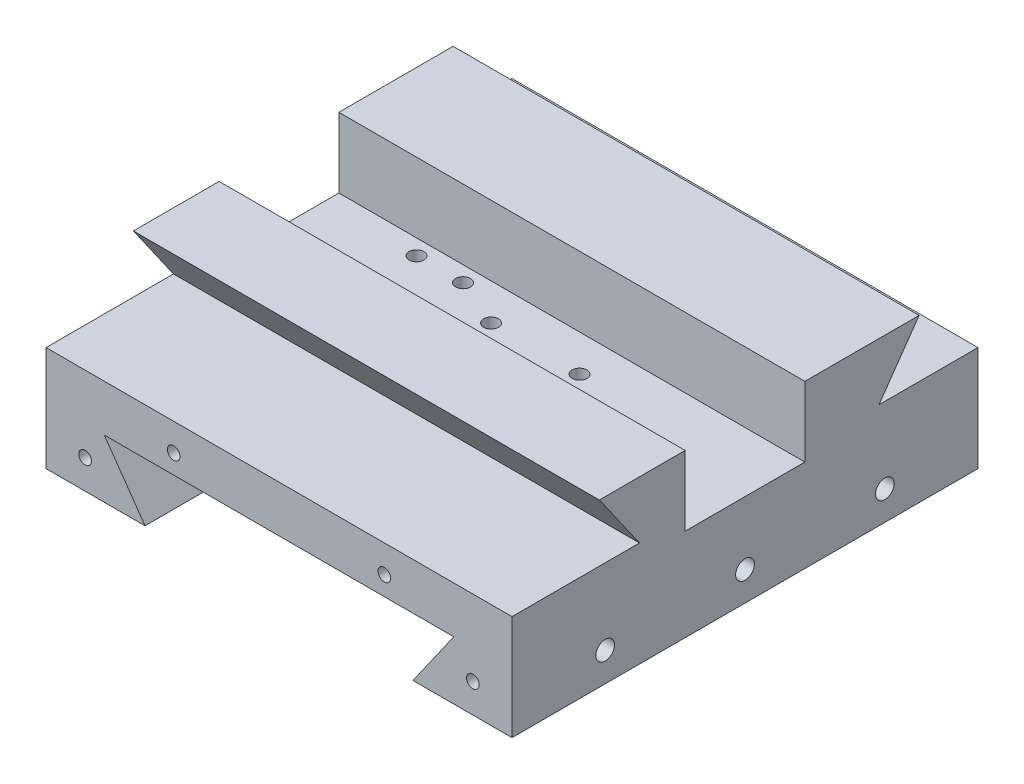
SolidWorks part; units mm, degrees
material "Ductile Iron"
ref_plane "Front Plane" through (0, 0, 0) normal (0, 0, 1) x (1, 0, 0)
ref_plane "Top Plane" through (0, 0, 0) normal (0, 1, 0) x (1, 0, 0)
ref_plane "Right Plane" through (0, 0, 0) normal (1, 0, 0) x (0, 0, -1)
sketch "Sketch10" plane through (0, 0, 0) normal (0, 0, 1) x (1, 0, 0)
  line B0 (-63.5, -15.875) -> (63.5, -15.875)
  line B1 (63.5, 0) -> (36.5092, 0)
  line B2 (36.5092, 0) -> (47.625, 15.875)
  line B3 (47.625, 15.875) -> (16.0563, 15.875)
  line B4 (-39.8731, 15.875) -> (-28.7573, 0)
  line B5 (-28.7573, 0) -> (-63.5, 0)
  line B6 (-63.5, 0) -> (-63.5, -15.875)
  line B7 (-36.5092, 0) -> (-47.625, 15.875)
  line B8 (-47.625, 15.875) -> (-39.8731, 15.875)
  line B9 (-16.0563, 15.875) -> (-16.0563, -3.175)
  line B10 (-16.0563, -3.175) -> (16.0563, -3.175)
  line B11 (16.0563, -3.175) -> (16.0563, 15.875)
  line B12 (-16.0563, 15.875) -> (-39.8731, 15.875)
  line B13 (-63.5, 0) -> (-63.5, 31.75)
  line B14 (-63.5, 31.75) -> (63.5, 31.75)
  line B15 (63.5, 31.75) -> (63.5, 0)
  line B16 (-16.0563, 15.875) -> (16.0563, 15.875)
  line B17 (0, 31.75) -> (0, -15.875) construction
  line B18 (-36.5092, 0) -> (36.5092, 0) construction
  line B19 (-28.702, 21.082) -> (28.702, 21.082) construction
  line B20 (-25.4, -8.001) -> (25.4, -8.001) construction
  line B21 (-25.4, -8.001) -> (-25.4, 7.9375) construction
  line B22 (25.4, -8.001) -> (25.4, 7.9375) construction
  line B23 (-52.832, 7.9375) -> (52.832, 7.9375) construction
  circle B24 centre (0, 6.35) radius 18.669 construction
sketch_block_instance "dovetail pair-1"
sketch_block "dovetail pair" parameters "D8"=37.338, "D1"=55, "D2"=127, "D3"=6.35, "D4"=15.875, "D5"=31.75, "D6"=95.25, "D7"=19.05, "D9"=55, "D10"=31.75, "D11"=50.8, "D12"=23.876, "D13"=7.874, "D14"=10.668, "D15"=34.798, "D16"=21.082, "D17"=7.9375
sketch "Sketch11" plane through (0, 0, 0) normal (1, 0, 0) x (0, 0, -1)
  line L0 (0, 31.75) -> (0, -15.875) construction
  line B0 (-63.5, 12.7) -> (63.5, 12.7)
  line B1 (63.5, 12.7) -> (63.5, 28.575)
  line B2 (63.5, 28.575) -> (36.5092, 28.575)
  line B3 (36.5092, 28.575) -> (47.625, 44.45)
  line B4 (47.625, 44.45) -> (16.0563, 44.45)
  line B5 (-39.8731, 44.45) -> (-28.7573, 28.575)
  line B6 (-28.7573, 28.575) -> (-63.5, 28.575)
  line B7 (-63.5, 28.575) -> (-63.5, 12.7)
  line B8 (-36.5092, 28.575) -> (-47.625, 44.45)
  line B9 (-47.625, 44.45) -> (-39.8731, 44.45)
  line B10 (-16.0563, 44.45) -> (-16.0563, 25.4)
  line B11 (-16.0563, 25.4) -> (16.0563, 25.4)
  line B12 (16.0563, 25.4) -> (16.0563, 44.45)
  line B13 (-16.0563, 44.45) -> (-39.8731, 44.45)
  line B14 (-63.5, 28.575) -> (-63.5, 60.325)
  line B15 (-63.5, 60.325) -> (63.5, 60.325)
  line B16 (63.5, 60.325) -> (63.5, 28.575)
  line B17 (-16.0563, 44.45) -> (16.0563, 44.45)
  line B18 (0, 60.325) -> (0, 12.7) construction
  line B19 (-36.5092, 28.575) -> (36.5092, 28.575) construction
  line B20 (-28.702, 49.657) -> (28.702, 49.657) construction
  line B21 (-25.4, 20.574) -> (25.4, 20.574) construction
  line B22 (-25.4, 20.574) -> (-25.4, 36.5125) construction
  line B23 (25.4, 20.574) -> (25.4, 36.5125) construction
  line B24 (-52.832, 36.5125) -> (52.832, 36.5125) construction
  circle B25 centre (0, 34.925) radius 18.669 construction
  dimension "D1" = 44.45
sketch_block_instance "dovetail pair-3"
sketch "female-dovetail-profile" plane through (0, 0, 0) normal (0, 0, 1) x (1, 0, 0)
  line L0 (-47.625, 15.875) -> (-39.8731, 15.875) construction
  line L1 (-16.0563, 15.875) -> (-39.8731, 15.875) construction
  line L2 (-16.0563, 15.875) -> (16.0563, 15.875) construction
  line L3 (47.625, 15.875) -> (16.0563, 15.875) construction
  line L4 (-47.625, 15.875) -> (-39.8731, 15.875)
  line L5 (-16.0563, 15.875) -> (-39.8731, 15.875)
  line L6 (-16.0563, 15.875) -> (16.0563, 15.875)
  line L7 (47.625, 15.875) -> (16.0563, 15.875)
  line L8 (-36.5092, 0) -> (-47.625, 15.875) construction
  line L9 (-63.5, 0) -> (-63.5, 31.75) construction
  line L10 (63.5, 31.75) -> (63.5, 0) construction
  line L11 (63.5, 0) -> (36.5092, 0) construction
  line L12 (36.5092, 0) -> (47.625, 15.875) construction
  line L13 (-36.5092, 0) -> (-47.625, 15.875)
  line L14 (-63.5, 0) -> (-63.5, 31.75)
  line L15 (63.5, 31.75) -> (63.5, 0)
  line L16 (63.5, 0) -> (36.5092, 0)
  line L17 (36.5092, 0) -> (47.625, 15.875)
  line L18 (-36.5092, 0) -> (-63.5, 0)
  line L20 (63.5, 31.75) -> (63.5, 44.45)
  line L21 (63.5, 44.45) -> (-63.5, 44.45)
  line L22 (-63.5, 44.45) -> (-63.5, 31.75)
  dimension "D1" = 44.45
extrude "x-carriage-extrude" add sketch "female-dovetail-profile" along normal mid plane 127
sketch "male-dovetail-shoulder-profile" plane through (0, 0, 0) normal (1, 0, 0) x (0, 0, -1)
  line L0 (-28.7573, 28.575) -> (-63.5, 28.575) construction
  line L1 (-39.8731, 44.45) -> (-28.7573, 28.575) construction
  line L2 (36.5092, 28.575) -> (47.625, 44.45) construction
  line L3 (63.5, 28.575) -> (36.5092, 28.575) construction
  line L4 (-28.7573, 28.575) -> (-63.5, 28.575)
  line L5 (-39.8731, 44.45) -> (-28.7573, 28.575) construction
  line L6 (36.5092, 28.575) -> (47.625, 44.45) construction
  line L7 (63.5, 28.575) -> (36.5092, 28.575)
  line L8 (-16.0563, 44.45) -> (-16.0563, 25.4) construction
  line L9 (-16.0563, 25.4) -> (16.0563, 25.4) construction
  line L10 (16.0563, 25.4) -> (16.0563, 44.45) construction
  line L11 (47.625, 44.45) -> (16.0563, 44.45) construction
  line L13 (-16.0563, 44.45) -> (-39.8731, 44.45) construction
  line L14 (-16.0563, 44.45) -> (-16.0563, 25.4) construction
  line L15 (-16.0563, 25.4) -> (16.0563, 25.4) construction
  line L16 (16.0563, 25.4) -> (16.0563, 44.45) construction
  line L17 (47.625, 44.45) -> (16.0563, 44.45) construction
  line L18 (-28.7573, 28.575) -> (-39.6952, 44.196)
  line L19 (-16.0563, 44.45) -> (-39.8731, 44.45) construction
  line L20 (-39.6952, 44.196) -> (-16.3103, 44.196)
  line L21 (-16.3103, 44.196) -> (-16.3103, 25.146)
  line L22 (-16.3103, 25.146) -> (16.3103, 25.146)
  line L23 (16.3103, 25.146) -> (16.3103, 44.196)
  line L24 (16.3103, 44.196) -> (47.4471, 44.196)
  line L25 (47.4471, 44.196) -> (36.5092, 28.575)
  line L26 (-63.5, 28.575) -> (-63.5, 44.45)
  line L27 (-63.5, 44.45) -> (63.5, 44.45)
  line L28 (63.5, 44.45) -> (63.5, 28.575)
  line L29 (0, 60.325) -> (0, 12.7) construction
  point P16 (0, 25.146)
  dimension "D2" = 0.254
  dimension "D3" = 0.254
  dimension "D1" = 0.254
extrude "y-guide-cut-extrude" cut sketch "male-dovetail-shoulder-profile" against normal mid plane 127
hole_wizard "#8-32 Tapped Hole1" positions "Sketch4" profile "Sketch5" tap size "#8-32" standard "ANSI Inch"
sketch "Sketch4" plane through (0, -15.875, 63.5) normal (0, 0, 1) x (1, 0, 0)
  point P32 (-52.832, 23.8125)
  point P34 (-28.702, 36.957)
  point P36 (28.702, 36.957)
  point P38 (52.832, 23.8125)
cosmetic thread "Hole Thread12" parameters "D1"=8.382, "D2"=4.1656
sketch "Sketch5" plane through (-52.832, 7.9375, 63.5) normal (1, 0, 0) x (0, -1, 0)
  line L0 (0, 0) -> (0, 13.3822)
  line L1 (0, 13.3822) -> (1.7272, 12.3444)
  line L2 (1.7272, 12.3444) -> (1.7272, 0)
  line L3 (1.7272, 0) -> (0, 0)
  line L4 (0, 13.3822) -> (-1.7272, 12.3444) construction
  line L5 (0, -6.35) -> (0, 107.95) construction
  dimension "Tap Drill Dia." = 3.4544
  dimension "Tap Drill Depth" = 12.3444
  dimension "Drill Angle" = 118
cosmetic thread "Hole Thread20" parameters "D1"=8.382, "D2"=4.1656
cosmetic thread "Hole Thread21" parameters "D1"=8.382, "D2"=4.1656
cosmetic thread "Hole Thread22" parameters "D1"=8.382, "D2"=4.1656
hole_wizard "#8-32 Tapped Hole2" positions "Sketch6" profile "Sketch7" tap size "#8-32" standard "ANSI Inch"
sketch "Sketch6" plane through (0, -15.875, -63.5) normal (0, 0, -1) x (-1, 0, 0)
  point P8 (-52.832, 23.8125)
  point P10 (-28.702, 36.957)
  point P12 (28.702, 36.957)
  point P14 (52.832, 23.8125)
cosmetic thread "Hole Thread15" parameters "D1"=8.382, "D2"=4.1656
sketch "Sketch7" plane through (52.832, 7.9375, -63.5) normal (1, 0, 0) x (0, 1, 0)
  line L0 (0, 0) -> (0, 13.4838)
  line L1 (0, 13.4838) -> (1.7272, 12.446)
  line L2 (1.7272, 12.446) -> (1.7272, 0)
  line L5 (1.7272, 0) -> (0, 0)
  line L10 (0, 13.4838) -> (-1.7272, 12.446) construction
  line L11 (0, -6.35) -> (0, 107.95) construction
  dimension "Tap Drill Dia." = 3.4544
  dimension "Tap Drill Depth" = 12.446
  dimension "Drill Angle" = 118
cosmetic thread "Hole Thread23" parameters "D1"=8.382, "D2"=4.1656
cosmetic thread "Hole Thread24" parameters "D1"=8.382, "D2"=4.1656
cosmetic thread "Hole Thread25" parameters "D1"=8.382, "D2"=4.1656
hole_wizard "gib screw 1/4-20 Tapped Hole1" positions "Sketch9" profile "Sketch8" tap size "1/4-20" standard "ANSI Inch" end condition up to next
sketch "Sketch9" plane through (0, 0, 0) normal (1, 0, 0) x (0, 0, -1)
  line L2 (0, 15.875) -> (0, 0) construction
  line L4 (63.5, 7.9375) -> (-63.5, 7.9375) construction
  line L7 (-38.1, 7.9375) -> (0, 7.9375) construction
  line L8 (63.5, 0) -> (63.5, 28.575) construction
  line L9 (-63.5, 15.875) -> (63.5, 15.875) construction
  line L10 (-63.5, 15.875) -> (63.5, 15.875)
  point P0 (-38.1, 7.9375)
  point P16 (0, 7.9375)
  point P22 (0, 7.9375)
  point P23 (38.1, 7.9375)
  dimension "D1" = 38.1
  dimension "D2" = 3
sketch "Sketch8" plane through (0, 7.9375, 38.1) normal (0, 1, 0) x (0, 0, 1)
  line L0 (0, 0) -> (0, 63.5)
  line L1 (0, 63.5) -> (2.5527, 63.5)
  line L2 (2.5527, 63.5) -> (2.5527, 0)
  line L5 (2.5527, 0) -> (0, 0)
  line L11 (0, -6.35) -> (0, 107.95) construction
  dimension "Thru Tap Drill Dia." = 5.1054
  dimension "Thru Tap Drill Depth" = 63.5
cosmetic thread "Hole Thread17" parameters "D2"=6.35
cosmetic thread "Hole Thread26" parameters "D2"=6.35
cosmetic thread "Hole Thread27" parameters "D2"=6.35
hole_wizard "#10-32 Tapped Hole1" positions "Sketch13" profile "Sketch12" tap size "#10-32" standard "ANSI Inch" end condition up to next
sketch "Sketch13" plane through (0, 25.146, 0) normal (0, 1, 0) x (1, 0, 0)
  line L1 (-12.065, -6.35) -> (12.065, -6.35) construction
  line L2 (-12.065, -6.35) -> (-12.065, 6.35) construction
  line L3 (-12.065, 6.35) -> (12.065, 6.35) construction
  line L4 (12.065, -6.35) -> (12.065, 6.35) construction
  line L6 (-38.1, -12.065) -> (-25.4, -12.065) construction
  line L7 (-38.1, -12.065) -> (-38.1, 12.065) construction
  line L8 (-38.1, 12.065) -> (-25.4, 12.065) construction
  line L9 (-25.4, -12.065) -> (-25.4, 12.065) construction
  line L10 (0, 16.3103) -> (0, -16.3103) construction
  line L11 (-63.5, 16.3103) -> (63.5, 16.3103) construction
  line L12 (-63.5, -16.3103) -> (63.5, -16.3103) construction
  line L13 (-63.5, 0) -> (63.5, 0) construction
  line L14 (-63.5, -16.3103) -> (-63.5, 16.3103) construction
  line L15 (63.5, -16.3103) -> (63.5, 16.3103) construction
  point P0 (-38.1, 12.065)
  point P2 (-38.1, -12.065)
  point P4 (-12.065, 6.35)
  point P6 (-25.4, 12.065)
  point P8 (-25.4, -12.065)
  point P10 (12.065, 6.35)
  point P12 (12.065, -6.35)
  point P14 (-12.065, -6.35)
  point P155 (0, 0)
  point P157 (0, -6.35)
  point P158 (12.065, 0)
  point P159 (-25.4, 0)
  dimension "D1" = 24.13
  dimension "D2" = 24.13
  dimension "D3" = 12.7
  dimension "D4" = 12.7
  dimension "D5" = 38.1
sketch "Sketch12" plane through (-38.1, 25.146, -12.065) normal (1, 0, 0) x (0, 0, 1)
  line L0 (0, 0) -> (0, 9.271)
  line L1 (0, 9.271) -> (2.0193, 9.271)
  line L2 (2.0193, 9.271) -> (2.0193, 0)
  line L5 (2.0193, 0) -> (0, 0)
  line L11 (0, -6.35) -> (0, 107.95) construction
  dimension "Thru Tap Drill Dia." = 4.0386
  dimension "Thru Tap Drill Depth" = 9.271
cosmetic thread "Hole Thread28" parameters "D2"=4.826
cosmetic thread "Hole Thread29" parameters "D2"=4.826
cosmetic thread "Hole Thread30" parameters "D2"=4.826
cosmetic thread "Hole Thread31" parameters "D2"=4.826
cosmetic thread "Hole Thread32" parameters "D2"=4.826
cosmetic thread "Hole Thread33" parameters "D2"=4.826
cosmetic thread "Hole Thread34" parameters "D2"=4.826
cosmetic thread "Hole Thread35" parameters "D2"=4.826
equation "\"dovetail-angle\" = 55"
equation "\"dovetail-stock-width\" = 5"
equation "\"dovetail-stock-height\" = 1.25"
equation "\"dovetail-depth\" = 0.5 * \"dovetail-stock-height\""
equation "\"dovetail-throat-width\" = \"dovetail-stock-width\" - (2 * \"dovetail-depth\")"
equation "\"delta-x\" = 6"
equation "\"delta-y\" = 3"
equation "\"delta-z\"= 2.5"
equation "\"gib-thickness\" = 0.25"
equation "\"x-slide-length\" = \"dovetail-stock-width\" + \"delta-x\""
equation "\"y-slide-length\" = \"dovetail-stock-width\" + \"delta-y\""
equation "\"dog-point-diam\" = .149"
equation "\"D1@female-dovetail-profile\"=\"dovetail-double-height\""
equation "\"D1@x-carriage-extrude\"=\"dovetail-stock-width\""
equation "\"dog-point-length\" = .067"
equation "\"dovetail-double-height\" = 2 * \"dovetail-depth\" + 0.5"
equation "\"D2@male-dovetail-shoulder-profile\"=\"acme_nut_clearance\""
equation "\"D3@male-dovetail-shoulder-profile\"=\"dovetail_male_clearance\""
equation "\"acme-major-diam\" = .5"
equation "\"acme-pitch-diam\" = 0.45"
equation "\"acme-minor-diam\" = 0.4"
equation "\"acme-nut-od\" = 1.47"
equation "\"acme-nut-length\" = 1"
equation "\"acme-nut-trim-height\" = .75"
equation "\"screw-bearing-od\" = 0.5"
equation "\"screw-bearing-length\" = .375"
equation "\"screw-bearing-id\" = .375"
equation "\"end-plate-thickness\" = \"screw-bearing-length\""
equation "\"screw-add-length\" = 2 * \"end-plate-thickness\" + 1 + 0.5"
equation "\"x-screw-length\" = \"x-slide-length\" + \"screw-add-length\""
equation "\"y-screw-length\" = \"y-slide-length\" + \"screw-add-length\""
equation "\"acme-nut-mount-hole-space-horz\" = 0.95"
equation "\"acme-nut-mount-hole-space-vert\" = 0.5 * \"acme-nut-length\""
equation "\"D2@dovetail pair\"=\"dovetail-stock-width\""
equation "\"D1@dovetail pair\"=\"dovetail-angle\""
equation "\"D3@dovetail pair\"=\"gib-thickness\""
equation "\"D4@dovetail pair\"=\"dovetail-depth\""
equation "\"D5@dovetail pair\"=\"dovetail-stock-height\""
equation "\"D6@dovetail pair\"=\"dovetail-throat-width\""
equation "\"D10@dovetail pair\"=\"dovetail-stock-height\""
equation "\"D7@dovetail pair\"=\"acme-nut-trim-height\""
equation "\"D8@dovetail pair\"=\"acme-nut-od\""
equation "\"D9@dovetail pair\"=\"dovetail-angle\""
equation "\"D17@dovetail pair\"=\"dovetail-depth\"/2"
equation "\"D1@Sketch11\"=\"dovetail-double-height\""
equation "\"acme-nut-trim-width\" = 1.25"
equation "\"vise-hole-center-dist\" = 6.75"
equation "\"wiper_plate_clearance\" = .03"
equation "\"dial-width\" = 0.5"
equation "\"quarter-twenty-free-fit\" = .2667"
equation "\"acme_nut_clearance\" = .01"
equation "\"dovetail_male_clearance\" = .01"
equation "\"D1@y-guide-cut-extrude\"=\"dovetail-stock-width\""
equation "\"D1@male-dovetail-shoulder-profile\"=\"acme_nut_clearance\""
equation "\"D1@Sketch13\"=\"acme-nut-mount-hole-space-horz\""
equation "\"D2@Sketch13\"=\"acme-nut-mount-hole-space-horz\""
equation "\"D3@Sketch13\"=\"acme-nut-mount-hole-space-vert\""
equation "\"D4@Sketch13\"=\"acme-nut-mount-hole-space-vert\""
